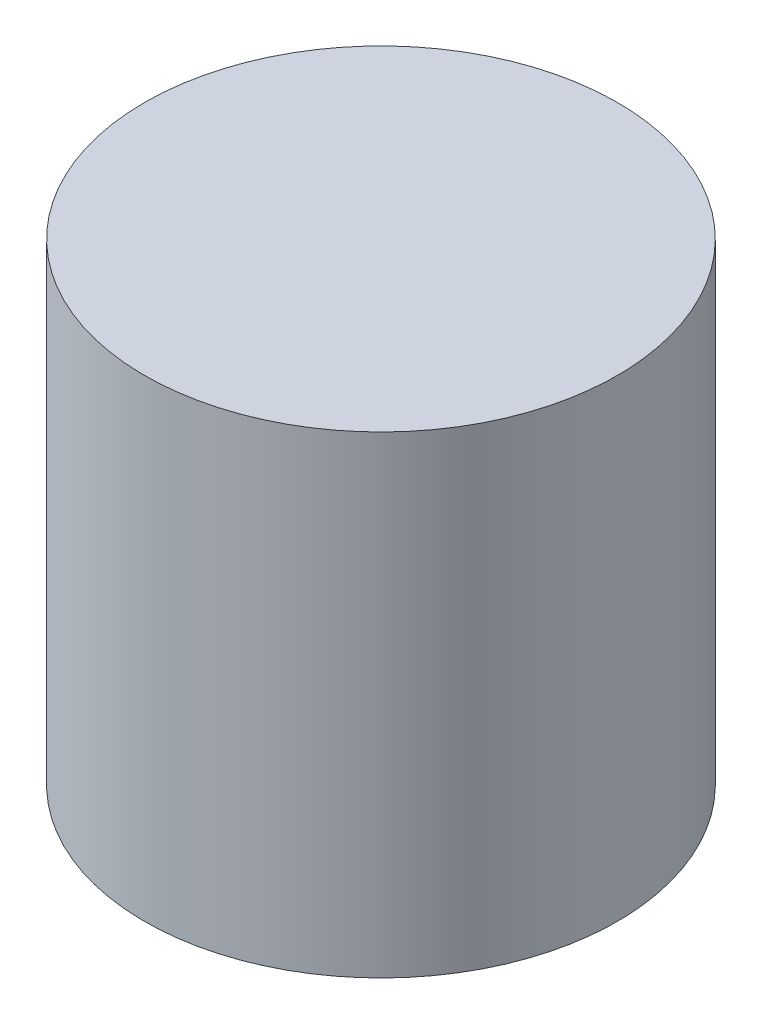
SolidWorks part; units mm, degrees
material "Acrylic (Medium-high impact)"
ref_plane "Front Plane" through (0, 0, 0) normal (0, 0, 1) x (1, 0, 0)
ref_plane "Top Plane" through (0, 0, 0) normal (0, 1, 0) x (1, 0, 0)
ref_plane "Right Plane" through (0, 0, 0) normal (1, 0, 0) x (0, 0, -1)
sketch "Sketch1" plane through (0, 0, 0) normal (0, 0, 1) x (1, 0, 0)
  line L0 (0, 50.8) -> (0, -50.8) construction
  line L1 (0, -50.8) -> (50.8, -50.8)
  line L2 (50.8, -50.8) -> (50.8, 50.8)
  line L3 (50.8, 50.8) -> (0, 50.8)
  line L4 (0, 44.45) -> (44.45, 44.45)
  line L5 (44.45, 44.45) -> (44.45, -44.45)
  line L6 (44.45, -44.45) -> (0, -44.45)
  dimension "D1" = 101.6
  dimension "D2" = 50.8
  dimension "D3" = 6.35
  dimension "D4" = 6.35
  dimension "D5" = 6.35
revolve "Revolve1" add sketch "Sketch1" angle 360 about L0 region at (25.4, 49.6641, 0)
